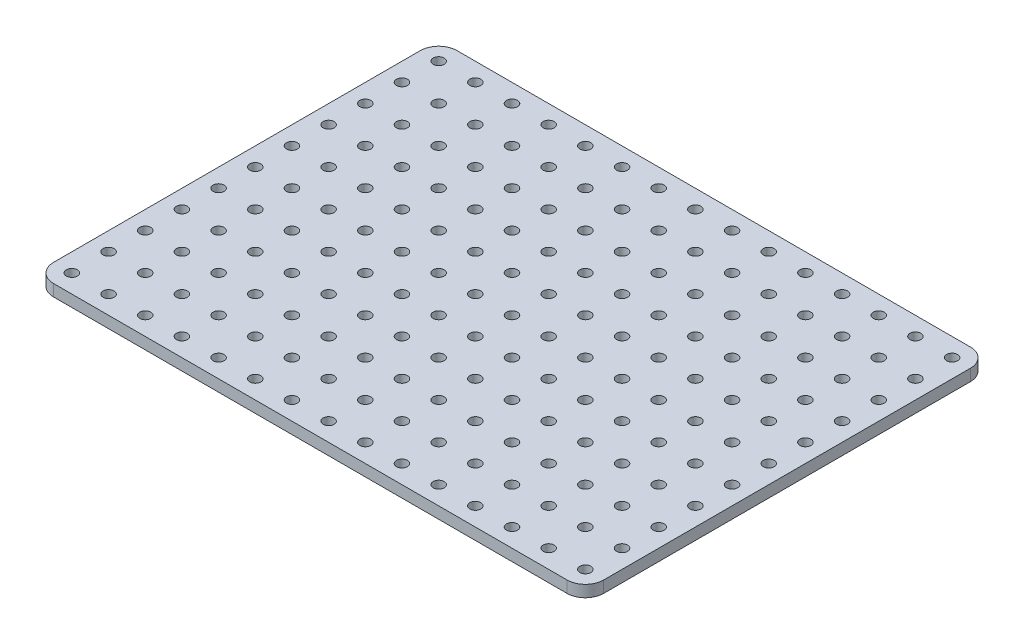
SolidWorks part; units mm, degrees
material "Balsa"
ref_plane "Front Plane" through (0, 0, 0) normal (0, 0, 1) x (1, 0, 0)
ref_plane "Top Plane" through (0, 0, 0) normal (0, 1, 0) x (1, 0, 0)
ref_plane "Right Plane" through (0, 0, 0) normal (1, 0, 0) x (0, 0, -1)
sketch "Sketch1" plane through (0, 0, 0) normal (0, 1, 0) x (1, 0, 0)
  line L1 (-5, -5) -> (5, -5)
  line L2 (-5, -5) -> (-5, 5)
  line L3 (-5, 5) -> (5, 5)
  line L4 (5, -5) -> (5, 5)
  line L5 (-5, -5) -> (5, 5) construction
  line L6 (-5, 5) -> (5, -5) construction
  circle A0 centre (0, 0) radius 1.5
  point P0 (0, 0)
  dimension "D1" = 3
  dimension "D2" = 10
extrude "Boss-Extrude1" add sketch "Sketch1" along normal mid plane 3.175
pattern_linear "LPattern1" count 15 spacing 10 along (1, 0, 0) count 11 spacing 10 along (0, 0, 1) of "Boss-Extrude1"
fillet "Fillet1" radius 5 4 edges at (-5, 0, -5) (-5, 0, 105) (145, 0, 105) (145, 0, -5)
